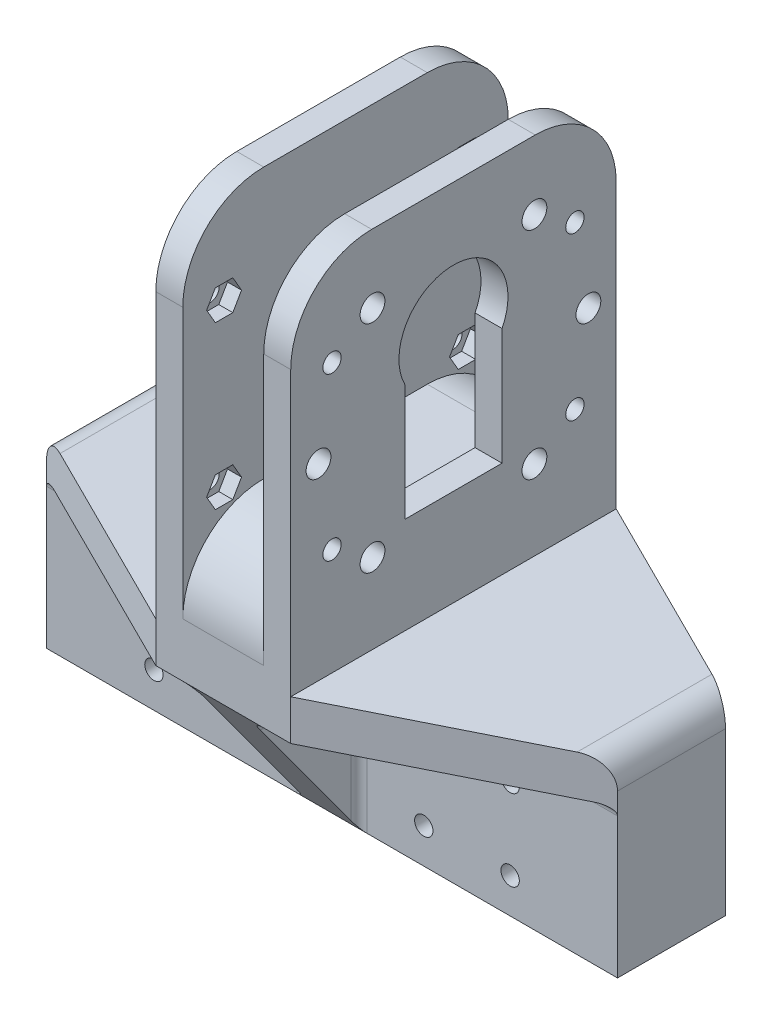
SolidWorks part; units mm, degrees
ref_plane "Front Plane" through (0, 0, 0) normal (0, 0, 1) x (1, 0, 0)
ref_plane "Top Plane" through (0, 0, 0) normal (0, 1, 0) x (1, 0, 0)
ref_plane "Right Plane" through (0, 0, 0) normal (1, 0, 0) x (0, 0, -1)
sketch "Sketch1" plane through (0, 0, 0) normal (0, 1, 0) x (1, 0, 0)
  line L0 (0, 10) -> (0, -10) construction
  line L1 (52.9, -10) -> (-52.9, -10)
  line L2 (52.9, -10) -> (52.9, 10)
  line L3 (52.9, 10) -> (-52.9, 10)
  line L4 (-52.9, -10) -> (-52.9, 10)
  line L5 (52.9, -10) -> (-52.9, 10) construction
  line L6 (52.9, 10) -> (-52.9, -10) construction
  line L7 (-38, 5.5) -> (-38, -5.5)
  line L8 (38, 5.5) -> (12, 5.5)
  line L9 (38, 5.5) -> (38, -5.5)
  line L10 (38, -5.5) -> (12, -5.5)
  line L11 (12, 5.5) -> (12, -5.5)
  line L12 (38, 5.5) -> (12, -5.5) construction
  line L13 (38, -5.5) -> (12, 5.5) construction
  line L14 (-38, 5.5) -> (-12, 5.5)
  line L15 (-12, 5.5) -> (-12, -5.5)
  line L16 (-38, -5.5) -> (-12, -5.5)
  point P0 (0, 0)
  point P8 (25, 0)
  dimension "D1" = 105.8
  dimension "D2" = 20
  dimension "D3" = 26
  dimension "D4" = 11
  dimension "D5" = 14.9
  dimension "D6" = 4.5
extrude "Boss-Extrude1" add sketch "Sketch1" along normal blind 30
sketch "Sketch2" plane through (0, 30, 0) normal (0, 1, 0) x (1, 0, 0)
  line L1 (52.9, -10) -> (-52.9, -10)
  line L2 (52.9, -10) -> (52.9, 10)
  line L3 (52.9, 10) -> (-52.9, 10)
  line L4 (-52.9, -10) -> (-52.9, 10)
  line L5 (52.9, -10) -> (-52.9, 10) construction
  line L6 (52.9, 10) -> (-52.9, -10) construction
  point P0 (0, 0)
extrude "Boss-Extrude2" add sketch "Sketch2" along normal blind 5
sketch "Sketch3" plane through (0, 0, -5.5) normal (0, 0, 1) x (1, 0, 0)
  line L0 (-33, 21.5) -> (-17, 21.5) construction
  line L1 (-33, 6.5) -> (-17, 6.5) construction
  line L2 (-17, 6.5) -> (-17, 21.5) construction
  line L3 (-33, 21.5) -> (-33, 6.5) construction
  line L4 (-38, 0) -> (-12, 0) construction
  line L5 (0, 0) -> (0, 35) construction
  line L6 (-52.9, 35) -> (52.9, 35) construction
  circle A0 centre (-33, 21.5) radius 1.7
  circle A1 centre (-17, 21.5) radius 1.7
  circle A2 centre (-33, 6.5) radius 1.7
  circle A3 centre (-17, 6.5) radius 1.7
  circle A4 centre (33, 6.5) radius 1.7
  circle A5 centre (33, 21.5) radius 1.7
  circle A6 centre (17, 21.5) radius 1.7
  circle A7 centre (17, 6.5) radius 1.7
  point P3 (-25, 6.5)
  point P10 (-25, 0)
  dimension "D1" = 3.4
  dimension "D2" = 3.4
  dimension "D3" = 3.4
  dimension "D4" = 3.4
  dimension "D5" = 16
  dimension "D6" = 15
  dimension "D7" = 6.5
extrude "Cut-Extrude1" cut sketch "Sketch3" against normal blind 5 and the other way blind 16
sketch "Sketch4" plane through (0, 0, 0) normal (1, 0, 0) x (0, 0, -1)
  line L0 (5.5, 30) -> (-5.5, 30) construction
  line L1 (15.15, 52.5) -> (-15.15, 52.5)
  line L2 (30.15, 37.5) -> (30.15, 27.5)
  line L3 (30.15, 27.5) -> (-30.15, 27.5)
  line L4 (-30.15, 37.5) -> (-30.15, 27.5)
  line L5 (30.15, 52.5) -> (-30.15, 27.5) construction
  line L6 (30.15, 27.5) -> (-30.15, 52.5) construction
  line L7 (-10, 35) -> (10, 35) construction
  arc A0 (-15.15, 52.5) -> (-30.15, 37.5) centre (-15.15, 37.5) ccw
  arc A1 (15.15, 52.5) -> (30.15, 37.5) centre (15.15, 37.5) cw
  point P0 (0, 40)
  dimension "D4" = 15
  dimension "D1" = 25
  dimension "D2" = 60.3
  dimension "D3" = 2.5
extrude "Boss-Extrude3" add sketch "Sketch4" along normal blind 7.5 and the other way blind 7.5
sketch "Sketch5" plane through (7.5, 0, 0) normal (1, 0, 0) x (0, 0, -1)
  line L0 (-22.5, 84.8) -> (-22.5, 54.8) construction
  line L1 (-30.15, 27.5) -> (30.15, 27.5)
  line L2 (-30.15, 27.5) -> (-30.15, 87.5)
  line L3 (-15.15, 102.5) -> (15.15, 102.5)
  line L4 (30.15, 27.5) -> (30.15, 87.5)
  line L5 (-15, 89.8) -> (-15, 49.8) construction
  line L6 (0, 102.5) -> (0, 27.5) construction
  line L7 (30.15, 69.8) -> (-30.15, 69.8) construction
  line L8 (0, 52.9) -> (0, 89.2) construction
  line L10 (9, 74.5163) -> (9, 52.9)
  line L11 (9, 52.9) -> (-9, 52.9)
  line L12 (-9, 74.5163) -> (-9, 52.9)
  line L13 (9, 74.5163) -> (-9, 52.9) construction
  line L14 (9, 52.9) -> (-9, 74.5163) construction
  line L15 (-15, 89.8) -> (15, 89.8) construction
  circle A0 centre (-15, 89.8) radius 2.3
  circle A1 centre (-22.5, 84.8) radius 1.7
  circle A2 centre (-22.5, 54.8) radius 1.7
  circle A3 centre (-15, 49.8) radius 2.3
  circle A4 centre (-25, 69.8) radius 2.3
  circle A5 centre (15, 89.8) radius 2.3
  circle A6 centre (22.5, 84.8) radius 1.7
  circle A7 centre (25, 69.8) radius 2.3
  circle A8 centre (22.5, 54.8) radius 1.7
  circle A9 centre (15, 49.8) radius 2.3
  arc A10 (15.15, 102.5) -> (30.15, 87.5) centre (15.15, 87.5) cw
  arc A11 (-30.15, 87.5) -> (-15.15, 102.5) centre (-15.15, 87.5) cw
  arc A12 (9, 74.5163) -> (-9, 74.5163) centre (0, 79.1) ccw
  point P20 (0, 63.7082)
  point P22 (-15, 69.8)
  point P23 (-22.5, 69.8)
  point P36 (30.15, 102.5)
  dimension "D2" = 4.6
  dimension "D3" = 4.6
  dimension "D4" = 4.6
  dimension "D5" = 3.4
  dimension "D6" = 3.4
  dimension "D13" = 15
  dimension "D15" = 20.2
  dimension "D1" = 75
  dimension "D7" = 15
  dimension "D8" = 22.5
  dimension "D9" = 25
  dimension "D10" = 32.7
  dimension "D11" = 15
  dimension "D12" = 20
  dimension "D14" = 36.3
  dimension "D16" = 18
  dimension "D17" = 0.6
extrude "Boss-Extrude4" add sketch "Sketch5" along normal blind 5
sketch "Sketch6" plane through (-7.5, 0, 0) normal (-1, 0, 0) x (0, 0, 1)
  line L0 (-15.15, 102.5) -> (15.15, 102.5) construction
  line L1 (-30.15, 27.5) -> (30.15, 27.5)
  line L2 (-30.15, 27.5) -> (-30.15, 87.5)
  line L3 (-15.15, 102.5) -> (15.15, 102.5)
  line L4 (30.15, 27.5) -> (30.15, 87.5)
  circle A0 centre (-22.5, 84.8) radius 1.7
  circle A1 centre (22.5, 84.8) radius 1.7
  circle A2 centre (22.5, 54.8) radius 1.7
  circle A3 centre (-22.5, 54.8) radius 1.7
  circle A4 centre (-22.5, 54.8) radius 1.7 construction
  circle A5 centre (-22.5, 84.8) radius 1.7 construction
  circle A6 centre (22.5, 84.8) radius 1.7 construction
  circle A7 centre (22.5, 54.8) radius 1.7 construction
  arc A8 (-30.15, 87.5) -> (-15.15, 102.5) centre (-15.15, 87.5) cw
  arc A9 (15.15, 102.5) -> (30.15, 87.5) centre (15.15, 87.5) cw
  circle A10 centre (0, 79.1) radius 5
  point P32 (30.15, 102.5)
  dimension "D1" = 15
  dimension "D2" = 10
extrude "Boss-Extrude5" add sketch "Sketch6" along normal blind 5
sketch "Sketch7" plane through (7.5, 0, 0) normal (-1, 0, 0) x (0, 0, 1)
  line L1 (25.7332, 54.8) -> (24.1166, 57.6)
  line L2 (24.1166, 57.6) -> (20.8834, 57.6)
  line L3 (20.8834, 57.6) -> (19.2668, 54.8)
  line L4 (19.2668, 54.8) -> (20.8834, 52)
  line L5 (20.8834, 52) -> (24.1166, 52)
  line L6 (24.1166, 52) -> (25.7332, 54.8)
  line L7 (25.7332, 84.8) -> (24.1166, 87.6)
  line L8 (24.1166, 87.6) -> (20.8834, 87.6)
  line L9 (20.8834, 87.6) -> (19.2668, 84.8)
  line L10 (19.2668, 84.8) -> (20.8834, 82)
  line L11 (20.8834, 82) -> (24.1166, 82)
  line L12 (24.1166, 82) -> (25.7332, 84.8)
  line L13 (-19.2668, 84.8) -> (-20.8834, 87.6)
  line L14 (-20.8834, 87.6) -> (-24.1166, 87.6)
  line L15 (-24.1166, 87.6) -> (-25.7332, 84.8)
  line L16 (-25.7332, 84.8) -> (-24.1166, 82)
  line L17 (-24.1166, 82) -> (-20.8834, 82)
  line L18 (-20.8834, 82) -> (-19.2668, 84.8)
  line L19 (-19.2668, 54.8) -> (-20.8834, 57.6)
  line L20 (-20.8834, 57.6) -> (-24.1166, 57.6)
  line L21 (-24.1166, 57.6) -> (-25.7332, 54.8)
  line L22 (-25.7332, 54.8) -> (-24.1166, 52)
  line L23 (-24.1166, 52) -> (-20.8834, 52)
  line L24 (-20.8834, 52) -> (-19.2668, 54.8)
  circle A0 centre (22.5, 54.8) radius 2.8 construction
  circle A1 centre (22.5, 84.8) radius 2.8 construction
  circle A2 centre (-22.5, 84.8) radius 2.8 construction
  circle A3 centre (-22.5, 54.8) radius 2.8 construction
  point P28 (-22.5, 57.6)
  dimension "D1" = 5.6
  dimension "D2" = 2.8
  dimension "D3" = 5.6
  dimension "D4" = 5.6
  dimension "D5" = 5.6
  dimension "D6" = 2.8
  dimension "D7" = 2.8
  dimension "D8" = 2.8
extrude "Cut-Extrude2" cut sketch "Sketch7" against normal blind 2.6 and the other way blind 2.7
sketch "Sketch8" plane through (-7.5, 0, 0) normal (1, 0, 0) x (0, 0, -1)
  line L1 (-19.2668, 84.8) -> (-20.8834, 87.6)
  line L2 (-20.8834, 87.6) -> (-24.1166, 87.6)
  line L3 (-24.1166, 87.6) -> (-25.7332, 84.8)
  line L4 (-25.7332, 84.8) -> (-24.1166, 82)
  line L5 (-24.1166, 82) -> (-20.8834, 82)
  line L6 (-20.8834, 82) -> (-19.2668, 84.8)
  line L7 (25.7332, 84.8) -> (24.1166, 87.6)
  line L8 (24.1166, 87.6) -> (20.8834, 87.6)
  line L9 (20.8834, 87.6) -> (19.2668, 84.8)
  line L10 (19.2668, 84.8) -> (20.8834, 82)
  line L11 (20.8834, 82) -> (24.1166, 82)
  line L12 (24.1166, 82) -> (25.7332, 84.8)
  line L13 (25.7332, 54.8) -> (24.1166, 57.6)
  line L14 (24.1166, 57.6) -> (20.8834, 57.6)
  line L15 (20.8834, 57.6) -> (19.2668, 54.8)
  line L16 (19.2668, 54.8) -> (20.8834, 52)
  line L17 (20.8834, 52) -> (24.1166, 52)
  line L18 (24.1166, 52) -> (25.7332, 54.8)
  line L19 (-19.2668, 54.8) -> (-20.8834, 57.6)
  line L20 (-20.8834, 57.6) -> (-24.1166, 57.6)
  line L21 (-24.1166, 57.6) -> (-25.7332, 54.8)
  line L22 (-25.7332, 54.8) -> (-24.1166, 52)
  line L23 (-24.1166, 52) -> (-20.8834, 52)
  line L24 (-20.8834, 52) -> (-19.2668, 54.8)
  circle A0 centre (-22.5, 84.8) radius 2.8 construction
  circle A1 centre (22.5, 84.8) radius 2.8 construction
  circle A2 centre (22.5, 54.8) radius 2.8 construction
  circle A3 centre (-22.5, 54.8) radius 2.8 construction
  dimension "D1" = 5.6
  dimension "D2" = 2.8
  dimension "D3" = 5.6
  dimension "D4" = 2.8
  dimension "D5" = 5.6
  dimension "D6" = 2.8
  dimension "D7" = 5.6
  dimension "D8" = 2.8
extrude "Cut-Extrude3" cut sketch "Sketch8" against normal blind 2.6 and the other way blind 2.7
sketch "Sketch10" plane through (0, 27.5, 0) normal (0, -1, 0) x (1, 0, 0)
  line L0 (12.5, -30.15) -> (52.9, -10)
rib "Rib1" sketch "Sketch10" sketch "Sketch10" thickness 7.5 extrusion direction parallel to sketch draft on no parameters "D1"=7.5
sketch "Sketch11" plane through (0, 27.5, 0) normal (0, -1, 0) x (1, 0, 0)
  line L0 (-12.5, -30.15) -> (-52.9, -10)
rib "Rib2" sketch "Sketch11" sketch "Sketch11" thickness 7.5 extrusion direction parallel to sketch draft on no parameters "D1"=7.5
sketch "Sketch12" plane through (0, 27.5, 0) normal (0, -1, 0) x (1, 0, 0)
  line L0 (12.5, 30.15) -> (52.9, 10)
rib "Rib3" sketch "Sketch12" sketch "Sketch12" thickness 7.5 extrusion direction parallel to sketch draft on no parameters "D1"=7.5
sketch "Sketch13" plane through (0, 27.5, 0) normal (0, -1, 0) x (1, 0, 0)
  line L0 (-12.5, 30.15) -> (-52.9, 10)
rib "Rib4" sketch "Sketch13" sketch "Sketch13" thickness 7.5 extrusion direction parallel to sketch draft on no parameters "D1"=7.5
sketch "Sketch15" plane through (0, 0, 0) normal (1, 0, 0) x (0, 0, -1)
  line L0 (30.15, 27.5) -> (10, 0)
rib "Rib5" sketch "Sketch15" sketch "Sketch15" thickness 10 extrusion direction parallel to sketch draft on no parameters "D1"=10
sketch "Sketch16" plane through (0, 0, 0) normal (1, 0, 0) x (0, 0, -1)
  line L0 (-30.15, 27.5) -> (-10, 0)
rib "Rib6" sketch "Sketch16" sketch "Sketch16" thickness 10 extrusion direction parallel to sketch draft on no parameters "D1"=10
sketch "Sketch17" plane through (0, 0, -10) normal (0, 0, -1) x (-1, 0, 0)
  line L0 (-33, 21.5) -> (33, 21.5) construction
  line L1 (36.2332, 21.5) -> (34.6166, 24.3)
  line L2 (34.6166, 24.3) -> (31.3834, 24.3)
  line L3 (31.3834, 24.3) -> (29.7668, 21.5)
  line L4 (29.7668, 21.5) -> (31.3834, 18.7)
  line L5 (31.3834, 18.7) -> (34.6166, 18.7)
  line L6 (34.6166, 18.7) -> (36.2332, 21.5)
  line L7 (36.2332, 6.5) -> (34.6166, 9.3)
  line L8 (34.6166, 9.3) -> (31.3834, 9.3)
  line L9 (31.3834, 9.3) -> (29.7668, 6.5)
  line L10 (29.7668, 6.5) -> (31.3834, 3.7)
  line L11 (31.3834, 3.7) -> (34.6166, 3.7)
  line L12 (34.6166, 3.7) -> (36.2332, 6.5)
  line L13 (-33, 6.5) -> (33, 6.5) construction
  line L14 (0, 6.5) -> (0, 21.5) construction
  line L15 (17, 21.5) -> (33, 21.5) construction
  line L16 (25, 21.5) -> (25, 6.5) construction
  line L17 (15.3834, 18.7) -> (13.7668, 21.5)
  line L18 (18.6166, 18.7) -> (15.3834, 18.7)
  line L19 (20.2332, 21.5) -> (18.6166, 18.7)
  line L20 (18.6166, 24.3) -> (20.2332, 21.5)
  line L21 (15.3834, 24.3) -> (18.6166, 24.3)
  line L22 (13.7668, 21.5) -> (15.3834, 24.3)
  line L23 (15.3834, 3.7) -> (13.7668, 6.5)
  line L24 (18.6166, 3.7) -> (15.3834, 3.7)
  line L25 (20.2332, 6.5) -> (18.6166, 3.7)
  line L26 (18.6166, 9.3) -> (20.2332, 6.5)
  line L27 (15.3834, 9.3) -> (18.6166, 9.3)
  line L28 (13.7668, 6.5) -> (15.3834, 9.3)
  line L29 (-34.6166, 3.7) -> (-36.2332, 6.5)
  line L30 (-31.3834, 3.7) -> (-34.6166, 3.7)
  line L31 (-29.7668, 6.5) -> (-31.3834, 3.7)
  line L32 (-31.3834, 9.3) -> (-29.7668, 6.5)
  line L33 (-34.6166, 9.3) -> (-31.3834, 9.3)
  line L34 (-36.2332, 6.5) -> (-34.6166, 9.3)
  line L35 (-34.6166, 18.7) -> (-36.2332, 21.5)
  line L36 (-31.3834, 18.7) -> (-34.6166, 18.7)
  line L37 (-29.7668, 21.5) -> (-31.3834, 18.7)
  line L38 (-31.3834, 24.3) -> (-29.7668, 21.5)
  line L39 (-34.6166, 24.3) -> (-31.3834, 24.3)
  line L40 (-36.2332, 21.5) -> (-34.6166, 24.3)
  line L41 (-18.6166, 18.7) -> (-15.3834, 18.7)
  line L42 (-20.2332, 21.5) -> (-18.6166, 18.7)
  line L43 (-18.6166, 24.3) -> (-20.2332, 21.5)
  line L44 (-15.3834, 24.3) -> (-18.6166, 24.3)
  line L45 (-13.7668, 21.5) -> (-15.3834, 24.3)
  line L46 (-15.3834, 18.7) -> (-13.7668, 21.5)
  line L47 (-18.6166, 3.7) -> (-15.3834, 3.7)
  line L48 (-20.2332, 6.5) -> (-18.6166, 3.7)
  line L49 (-18.6166, 9.3) -> (-20.2332, 6.5)
  line L50 (-15.3834, 9.3) -> (-18.6166, 9.3)
  line L51 (-13.7668, 6.5) -> (-15.3834, 9.3)
  line L52 (-15.3834, 3.7) -> (-13.7668, 6.5)
  circle A0 centre (33, 21.5) radius 2.8 construction
  circle A1 centre (33, 6.5) radius 2.8 construction
  dimension "D1" = 5.6
  dimension "D2" = 2.8
  dimension "D3" = 5.6
  dimension "D4" = 2.8
extrude "Cut-Extrude4" cut sketch "Sketch17" against normal blind 2.6
fillet "Fillet1" radius 1.5 8 edges at (-5, 13.75, -10) (-28.95, 27.5, -10) (28.95, 27.5, -10) (5, 13.75, -10) (-5, 13.75, 10) (-28.95, 27.5, 10) (5, 13.75, 10) (28.95, 27.5, 10)
fillet "Fillet2" radius 2.5 8 edges at (5.4393, 27.0607, -10.4393) (-5.4393, 27.0607, -10.4393) (-5.4393, 27.0607, 10.4393) (5.4393, 27.0607, 10.4393) (5, 27.5, 20.825) (-5, 27.5, 20.825) (-5, 27.5, -20.825) (5, 27.5, -20.825)
fillet "Fillet3" radius 5 2 edges at (-52.9, 35, 0) (52.9, 35, 0)
